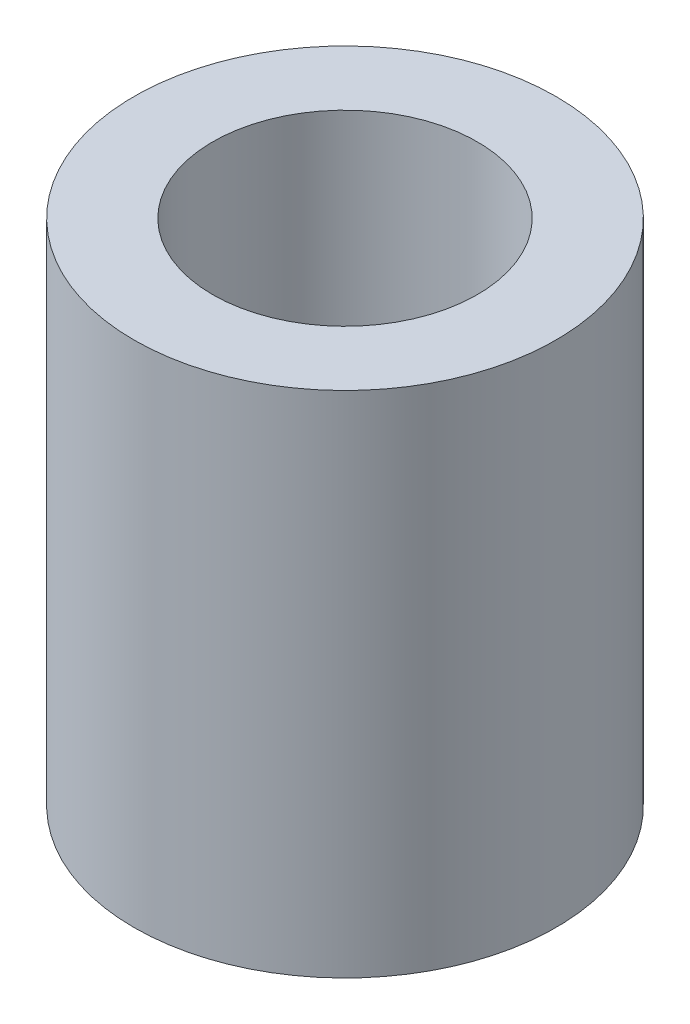
SolidWorks part; units mm, degrees
ref_plane "Front Plane" through (0, 0, 0) normal (0, 0, 1) x (1, 0, 0)
ref_plane "Top Plane" through (0, 0, 0) normal (0, 1, 0) x (1, 0, 0)
ref_plane "Right Plane" through (0, 0, 0) normal (1, 0, 0) x (0, 0, -1)
sketch "Sketch1" plane through (0, 0, 0) normal (0, 1, 0) x (1, 0, 0)
  circle A0 centre (0, 0) radius 2.55
  circle A1 centre (0, 0) radius 1.6
  dimension "D1" = 5.1
  dimension "D2" = 3.2
extrude "Boss-Extrude1" add sketch "Sketch1" along normal blind 6.15
